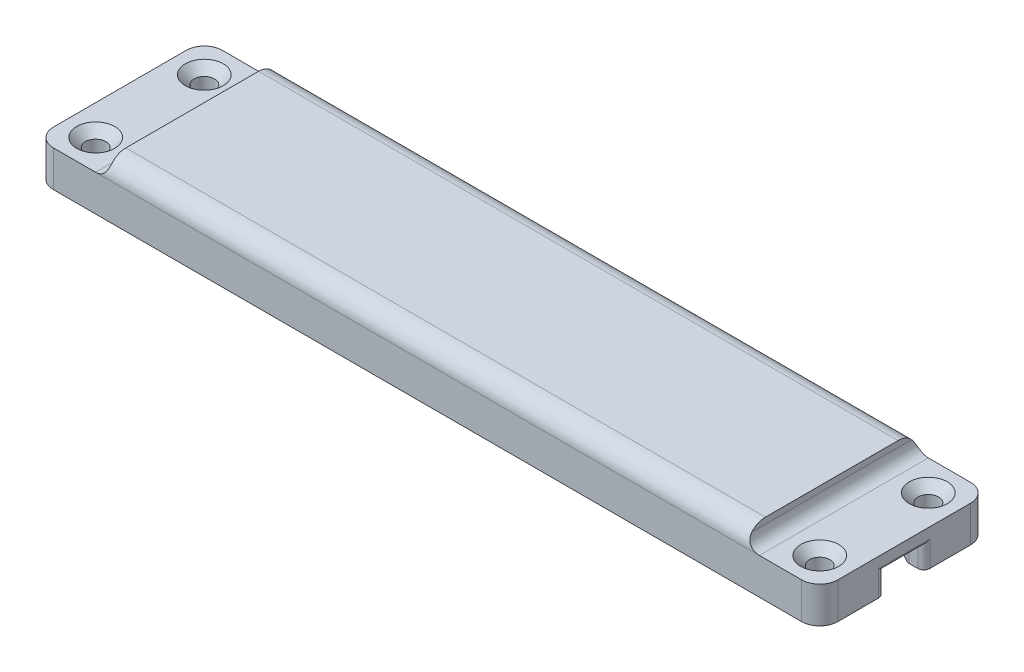
SolidWorks part; units mm, degrees
ref_plane "Front Plane" through (0, 0, 0) normal (0, 0, 1) x (1, 0, 0)
ref_plane "Top Plane" through (0, 0, 0) normal (0, 1, 0) x (1, 0, 0)
ref_plane "Right Plane" through (0, 0, 0) normal (1, 0, 0) x (0, 0, -1)
sketch "Sketch1" plane through (0, 0, 0) normal (0, 1, 0) x (1, 0, 0)
  line L1 (65, -14) -> (-65, -14)
  line L2 (65, -14) -> (65, 14)
  line L3 (65, 14) -> (-65, 14)
  line L4 (-65, -14) -> (-65, 14)
  line L5 (65, -14) -> (-65, 14) construction
  line L6 (65, 14) -> (-65, -14) construction
  point P0 (0, 0)
  dimension "D1" = 28
  dimension "D2" = 130
extrude "Boss-Extrude1" add sketch "Sketch1" along normal blind 9
sketch "Sketch2" plane through (0, 0, 0) normal (0, 1, 0) x (1, 0, 0)
  line L0 (-51, 7.5) -> (-56, 3.25)
  line L1 (27, -11.85) -> (-27, -11.85)
  line L2 (27, -11.85) -> (27, 11.85)
  line L3 (27, 11.85) -> (-27, 11.85)
  line L4 (-27, -11.85) -> (-27, 11.85)
  line L5 (27, -11.85) -> (-27, 11.85) construction
  line L6 (27, 11.85) -> (-27, -11.85) construction
  line L7 (55.3, -7.25) -> (27, -7.25)
  line L8 (55.3, -7.25) -> (55.3, 7.25)
  line L9 (55.3, 7.25) -> (27, 7.25)
  line L10 (27, -7.25) -> (27, 7.25)
  line L11 (55.3, -7.25) -> (27, 7.25) construction
  line L12 (55.3, 7.25) -> (27, -7.25) construction
  line L13 (-27, -7.5) -> (-51, -7.5)
  line L14 (-27, -7.5) -> (-27, 7.5)
  line L15 (-27, 7.5) -> (-51, 7.5)
  line L16 (-51, -7.5) -> (-51, 7.5)
  line L17 (-27, -7.5) -> (-51, 7.5) construction
  line L18 (-27, 7.5) -> (-51, -7.5) construction
  line L19 (-56, 3.25) -> (-65, 3.25)
  line L20 (-65, 14) -> (-65, -14) construction
  line L21 (-65, 3.25) -> (-65, -3.25)
  line L22 (-65, -3.25) -> (-56, -3.25)
  line L23 (-56, -3.25) -> (-51, -7.5)
  line L24 (55.3, 7.25) -> (62.3, 3.25)
  line L25 (62.3, 3.25) -> (65, 3.25)
  line L26 (65, -14) -> (65, 14) construction
  line L27 (65, 3.25) -> (65, -3.25)
  line L28 (65, -3.25) -> (62.3, -3.25)
  line L29 (62.3, -3.25) -> (55.3, -7.25)
  line L30 (-75.479, 0) -> (84.6073, 0) construction
  point P0 (0, 0)
  point P6 (41.15, 0)
  point P12 (-39, 0)
  dimension "D1" = 54
  dimension "D2" = 23.7
  dimension "D3" = 14.5
  dimension "D4" = 28.3
  dimension "D5" = 15
  dimension "D6" = 24
  dimension "D7" = 7
  dimension "D8" = 7
  dimension "D9" = 6.5
  dimension "D10" = 5
  dimension "D11" = 6.5
extrude "Cut-Extrude1" cut sketch "Sketch2" along normal blind 7 contours L4 L1 L2 L3 region at (0, 0, 0)
extrude "Cut-Extrude2" cut sketch "Sketch2<3>" along normal blind 3.75 contours L8 L9 L2 L7 | L29 L28 L27 L25 L24 L8 region at (41.15, 0, 0) region at (59.3761, 0, 0)
sketch "Sketch2<3>" plane through (0, 0, 0) normal (0, 1, 0) x (1, 0, 0) same geometry as "Sketch2"
extrude "Cut-Extrude3" cut sketch "Sketch2<4>" along normal blind 3.6 contours L16 L13 L4 L15 | L22 L23 L16 L0 L19 L21 region at (-56.9903, 0, 0) region at (-39, 0, 0)
sketch "Sketch2<4>" plane through (0, 0, 0) normal (0, 1, 0) x (1, 0, 0) same geometry as "Sketch2"
fillet "Fillet1" radius 1 20 edges at (65, 1.875, -3.25) (65, 1.875, 3.25) (-65, 1.8, -3.25) (-65, 1.8, 3.25) (-56, 1.8, 3.25) (-56, 1.8, -3.25) (-51, 1.8, -7.5) (-51, 1.8, 7.5) (-27, 1.8, -7.5) (-27, 1.8, 7.5) (55.3, 1.875, -7.25) (62.3, 1.875, -3.25) (62.3, 1.875, 3.25) (55.3, 1.875, 7.25) (27, 1.875, -7.25) (27, 1.875, 7.25) (-27, 3.5, -11.85) (-27, 3.5, 11.85) (27, 3.5, 11.85) (27, 3.5, -11.85)
fillet "Fillet2" radius 0.5 12 edges at (-26.7071, 7, 11.5571) (0, 7, 11.85) (26.7071, 7, 11.5571) (26.7071, 7, -11.5571) (0, 7, -11.85) (-26.7071, 7, -11.5571) (-65, 3.6, 0) (65, 3.75, 0) (27, 7, 0) (27, 3.75, 0) (-27, 3.6, 0) (-27, 7, 0)
fillet "Fillet3" radius 3 8 edges at (-65, 9, 0) (-65, 4.5, -14) (-65, 4.5, 14) (65, 4.5, 14) (65, 4.5, -14) (65, 9, 0) (0, 9, 14) (0, 9, -14)
sketch "Sketch3" plane through (0, 0, 0) normal (0, 1, 0) x (1, 0, 0)
  line L0 (-62, -14) -> (62, -14) construction
  line L1 (-65, -4.25) -> (-65, -11) construction
  line L2 (-65, 11) -> (-65, 4.25) construction
  line L3 (62, 14) -> (-62, 14) construction
  line L4 (65, -11) -> (65, -4.25) construction
  line L5 (65, 4.25) -> (65, 11) construction
  circle A0 centre (-60, -9) radius 1.7
  circle A1 centre (60, -9) radius 1.7
  circle A2 centre (60, 9) radius 1.7
  circle A3 centre (-60, 9) radius 1.7
  dimension "D1" = 3.4
  dimension "D2" = 5
  dimension "D3" = 5
  dimension "D4" = 5
  dimension "D5" = 5
  dimension "D6" = 5
  dimension "D7" = 5
  dimension "D8" = 5
  dimension "D9" = 5
extrude "Cut-Extrude4" cut sketch "Sketch3" along normal blind 13.6
ref_axis "Axis1" through (-60, 9, 9) along (0, -1, 0)
ref_axis "Axis2" through (-60, 9, -9) along (0, -1, 0)
ref_axis "Axis3" through (60, 9, 9) along (0, -1, 0)
ref_axis "Axis4" through (60, 9, -9) along (0, -1, 0)
ref_plane "Plane2" through (0, 0, 9) normal (0, 0, 1) x (1, 0, 0)
sketch "Sketch4" plane through (0, 0, 9) normal (0, 0, 1) x (1, 0, 0)
  line L0 (-60, 6) -> (-56.85, 6)
  line L1 (-60, 9) -> (-60, 0) construction
  line L2 (-56.85, 6) -> (-58.3, 4.55)
  line L3 (-58.3, 4.55) -> (-60, 4.55)
  line L4 (-60, 4.55) -> (-60, 6)
  line L5 (-62, 9) -> (62, 9) construction
  line L6 (60, 6) -> (63.15, 6)
  line L7 (63.15, 6) -> (61.7, 4.55)
  line L8 (61.7, 4.55) -> (60, 4.55)
  line L9 (60, 4.55) -> (60, 6)
  line L10 (60, 9) -> (60, 0) construction
  dimension "D1" = 3.15
  dimension "D2" = 1.7
  dimension "D3" = 1.45
  dimension "D4" = 135
  dimension "D5" = 3.15
  dimension "D6" = 1.7
  dimension "D7" = 1.45
  dimension "D8" = 135
  dimension "D9" = 3
  dimension "D10" = 3
revolve "Cut-Revolve1" cut sketch "Sketch4" angle 360 about axis through (60, 9, 9) along (0, -1, 0) region at (61.2486, 5.3473, 9)
revolve "Cut-Revolve2" cut sketch "Sketch4<3>" angle 360 about axis through (-60, 9, 9) along (0, -1, 0) region at (-58.7514, 5.3473, 9)
sketch "Sketch4<3>" plane through (0, 0, 9) normal (0, 0, 1) x (1, 0, 0) same geometry as "Sketch4"
ref_plane "Plane3" through (0, 0, -9) normal (0, 0, 1) x (1, 0, 0)
sketch "Sketch5" plane through (0, 0, -9) normal (0, 0, 1) x (1, 0, 0)
  line L0 (-60, 6) -> (-56.85, 6)
  line L1 (-56.85, 6) -> (-58.3, 4.55)
  line L2 (-58.3, 4.55) -> (-60, 4.55)
  line L3 (-60, 4.55) -> (-60, 6)
  line L5 (-60, 9) -> (-60, 0) construction
  line L6 (60, 6) -> (63.15, 6)
  line L7 (63.15, 6) -> (61.7, 4.55)
  line L8 (61.7, 4.55) -> (60, 4.55)
  line L9 (60, 4.55) -> (60, 6)
  line L11 (60, 9) -> (60, 0) construction
  line L12 (-62, 9) -> (62, 9) construction
  dimension "D1" = 3.15
  dimension "D2" = 1.7
  dimension "D3" = 1.45
  dimension "D4" = 135
  dimension "D5" = 3.15
  dimension "D6" = 1.7
  dimension "D7" = 1.45
  dimension "D8" = 135
  dimension "D9" = 3
  dimension "D10" = 3
revolve "Cut-Revolve3" cut sketch "Sketch5" angle 360 about axis through (60, 9, -9) along (0, -1, 0) region at (61.2486, 5.3473, -9)
revolve "Cut-Revolve4" cut sketch "Sketch5<3>" angle 360 about axis through (-60, 9, -9) along (0, -1, 0) region at (-58.7514, 5.3473, -9)
sketch "Sketch5<3>" plane through (0, 0, -9) normal (0, 0, 1) x (1, 0, 0) same geometry as "Sketch5"
ref_plane "Plane4" through (0, 9, 0) normal (0, 1, 0) x (1, 0, 0)
sketch "Sketch6" plane through (0, 9, 0) normal (0, 1, 0) x (1, 0, 0)
  line L1 (-53, -14) -> (-65, -14)
  line L2 (-53, -14) -> (-53, 14)
  line L3 (-53, 14) -> (-65, 14)
  line L4 (-65, -14) -> (-65, 14)
  line L5 (-53, -14) -> (-65, 14) construction
  line L6 (-53, 14) -> (-65, -14) construction
  line L7 (-65, -11) -> (-65, 11) construction
  line L8 (62, -14) -> (-62, -14) construction
  line L9 (0, 24.0191) -> (0, -24.0191) construction
  line L10 (53, 14) -> (65, -14) construction
  line L11 (53, -14) -> (65, 14) construction
  line L12 (65, -14) -> (65, 14)
  line L13 (53, 14) -> (65, 14)
  line L14 (53, -14) -> (53, 14)
  line L15 (53, -14) -> (65, -14)
  point P0 (-59, 0)
  point P16 (59, 0)
  dimension "D1" = 12
  dimension "D2" = 28
extrude "Cut-Extrude5" cut sketch "Sketch6" against normal blind 3
fillet "Fillet4" radius 2 2 edges at (53, 6, 0) (-53, 6, 0)
